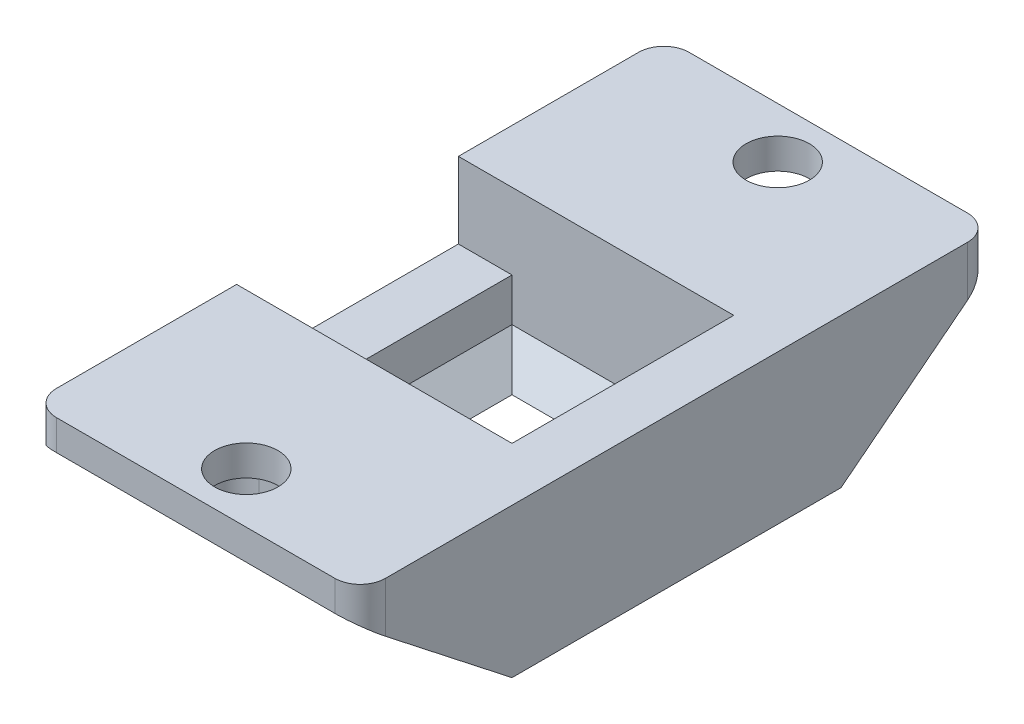
SolidWorks part; units mm, degrees
ref_plane "Front Plane" through (0, 0, 0) normal (0, 0, 1) x (1, 0, 0)
ref_plane "Top Plane" through (0, 0, 0) normal (0, 1, 0) x (1, 0, 0)
ref_plane "Right Plane" through (0, 0, 0) normal (1, 0, 0) x (0, 0, -1)
sketch "Sketch1" plane through (0, 0, 0) normal (0, 1, 0) x (1, 0, 0)
  line L1 (-4.3815, 4.3815) -> (4.3815, 4.3815)
  line L2 (-4.3815, 4.3815) -> (-4.3815, -4.3815)
  line L3 (-4.3815, -4.3815) -> (4.3815, -4.3815)
  line L4 (4.3815, 4.3815) -> (4.3815, -4.3815)
  line L5 (-4.3815, 4.3815) -> (4.3815, -4.3815) construction
  line L6 (-4.3815, -4.3815) -> (4.3815, 4.3815) construction
  line L7 (-2.8815, -2.8815) -> (2.8815, -2.8815)
  line L8 (-2.8815, -2.8815) -> (-2.8815, 2.8815)
  line L9 (-2.8815, 2.8815) -> (2.8815, 2.8815)
  line L10 (2.8815, -2.8815) -> (2.8815, 2.8815)
  line L11 (-2.8815, -2.8815) -> (2.8815, 2.8815) construction
  line L12 (-2.8815, 2.8815) -> (2.8815, -2.8815) construction
  point P0 (0, 0)
  point P6 (0, 0)
  dimension "D2" = 8.763
  dimension "D3" = 1.5
extrude "Boss-Extrude1" add sketch "Sketch1" along normal blind 1.2
sketch "Sketch2" plane through (0, 0, 0) normal (0, -1, 0) x (1, 0, 0)
  line L1 (-6.5, 6.5) -> (6.5, 6.5)
  line L2 (-6.5, 6.5) -> (-6.5, -6.5)
  line L3 (-6.5, -6.5) -> (6.5, -6.5)
  line L4 (4.3815, -4.3815) -> (4.3815, 4.3815)
  line L5 (4.3815, 4.3815) -> (-4.3815, 4.3815)
  line L6 (-4.3815, 4.3815) -> (-4.3815, -4.3815)
  line L7 (-4.3815, -4.3815) -> (4.3815, -4.3815)
  line L8 (4.3815, -4.3815) -> (4.3815, 4.3815)
  line L9 (4.3815, 4.3815) -> (-4.3815, 4.3815)
  line L10 (-4.3815, 4.3815) -> (-4.3815, -4.3815)
  line L11 (-4.3815, -4.3815) -> (4.3815, -4.3815)
  line L12 (6.5, 6.5) -> (6.5, -6.5)
  line L13 (-6.5, 6.5) -> (6.5, -6.5) construction
  line L14 (-6.5, -6.5) -> (6.5, 6.5) construction
  point P2 (0, 0)
  dimension "D2" = 13
  dimension "D1" = 0
extrude "Boss-Extrude3" add sketch "Sketch2" against normal offset from surface (5.9 mm away) 4.7 up to face at (0, 1.2, 0) offset beyond the face yes
chamfer "Chamfer1" distance 1.5 angle 45 4 edges at (0, 1.2, -2.8815) (2.8815, 1.2, 0) (0, 1.2, 2.8815) (-2.8815, 1.2, 0)
sketch "Sketch3" plane through (0, 5.9, 0) normal (0, 1, 0) x (1, 0, 0)
  line L0 (0, 6.5) -> (0, 12.5) construction
  line L1 (-6.5, 6.5) -> (6.5, 6.5)
  line L2 (-6.5, 6.5) -> (-6.5, 12.5)
  line L3 (-6.5, 12.5) -> (6.5, 12.5)
  line L4 (6.5, 6.5) -> (6.5, 12.5)
  circle A0 centre (0, 10.5) radius 1.25
  point P10 (0, 0)
  dimension "D3" = 2.5
  dimension "D1" = 10.5
  dimension "D2" = 12.5
extrude "Boss-Extrude4" add sketch "Sketch3" against normal blind 1.2
mirror "Mirror1" about plane through (0, 0, 0) normal (0, 0, 1) of "Boss-Extrude4"
sketch "Sketch5" plane through (-6.5, 0, 0) normal (-1, 0, 0) x (0, 0, 1)
  line L0 (6.5, 4.7) -> (6.5, 0) construction
  line L1 (12.5, 4.7) -> (6.5, 4.7) construction
  line L2 (-6.5, 4.7) -> (-6.5, 0) construction
  line L3 (-12.5, 4.7) -> (-6.5, 4.7) construction
  line L4 (6.5, 4.7) -> (6.5, 0)
  line L5 (12.5, 4.7) -> (6.5, 4.7)
  line L6 (-6.5, 4.7) -> (-6.5, 0)
  line L7 (-12.5, 4.7) -> (-6.5, 4.7)
  line L8 (12.5, 4.7) -> (6.5, 0)
  line L9 (-6.5, 0) -> (-12.5, 4.7)
extrude "Boss-Extrude5" add sketch "Sketch5" against normal blind 2
mirror "Mirror2" about plane through (0, 0, 0) normal (1, 0, 0) of "Boss-Extrude5"
fillet "Fillet1" radius 1 8 edges at (-6.5, 5.3, 12.5) (6.5, 5.3, 12.5) (-6.5, 5.3, -12.5) (6.5, 5.3, -12.5) (-4.5, 2.35, -6.5) (4.5, 2.35, -6.5) (-4.5, 2.35, 6.5) (4.5, 2.35, 6.5)
sketch "Sketch4" plane through (-6.5, 0, 0) normal (-1, 0, 0) x (0, 0, 1)
  line L0 (0, 0) -> (0, 5.9) construction
  line L1 (6.5, 0) -> (-6.5, 0) construction
  line L2 (11.5, 5.9) -> (-11.5, 5.9) construction
  line L4 (4.3815, 2.9) -> (-4.3815, 2.9)
  line L5 (4.3815, 2.9) -> (4.3815, 5.9)
  line L6 (4.3815, 5.9) -> (-4.3815, 5.9)
  line L7 (-4.3815, 2.9) -> (-4.3815, 5.9)
  line L8 (4.3815, 2.9) -> (-4.3815, 5.9) construction
  line L9 (4.3815, 5.9) -> (-4.3815, 2.9) construction
  point P6 (0, 4.4)
  dimension "D1" = 8.763
  dimension "D2" = 3
extrude "Cut-Extrude1" cut sketch "Sketch4" against normal up to next
